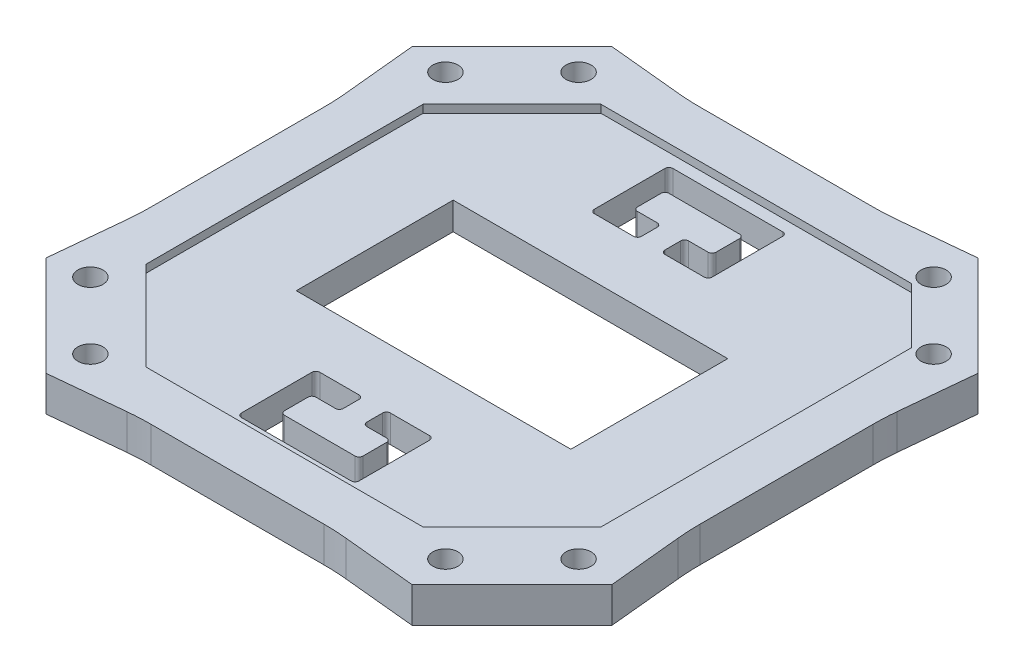
SolidWorks part; units mm, degrees
ref_plane "Front Plane" through (0, 0, 0) normal (0, 0, 1) x (1, 0, 0)
ref_plane "Top Plane" through (0, 0, 0) normal (0, 1, 0) x (1, 0, 0)
ref_plane "Right Plane" through (0, 0, 0) normal (1, 0, 0) x (0, 0, -1)
sketch "Sketch2" plane through (0, 0, 0) normal (0, 1, 0) x (1, 0, 0)
  line L0 (0, 0) -> (84.8528, 84.8528) construction
  line L1 (35, -35) -> (-35, -35) construction
  line L2 (35, -35) -> (35, 35) construction
  line L3 (35, 35) -> (-35, 35) construction
  line L4 (-35, -35) -> (-35, 35) construction
  line L5 (35, -35) -> (-35, 35) construction
  line L6 (35, 35) -> (-35, -35) construction
  line L7 (0, 35) -> (0, -35) construction
  line L8 (-12.5, 35) -> (12.5, 35)
  line L9 (35, 12.5) -> (35, -12.5)
  line L10 (12.5, -35) -> (-12.5, -35)
  line L11 (-35, -12.5) -> (-35, 12.5)
  line L12 (20.5061, 33.234) -> (33.234, 20.5061) construction
  line L13 (23.3345, 36.0624) -> (36.0624, 23.3345)
  line L14 (12.5, 35) -> (23.3345, 36.0624)
  line L15 (36.0624, 23.3345) -> (35, 12.5)
  line L16 (35, -12.5) -> (36.0624, -23.3345)
  line L17 (36.0624, -23.3345) -> (23.3345, -36.0624)
  line L18 (23.3345, -36.0624) -> (12.5, -35)
  line L19 (-12.5, -35) -> (-23.3345, -36.0624)
  line L20 (-23.3345, -36.0624) -> (-36.0624, -23.3345)
  line L21 (-36.0624, -23.3345) -> (-35, -12.5)
  line L22 (-35, 12.5) -> (-36.0624, 23.3345)
  line L23 (-36.0624, 23.3345) -> (-23.3345, 36.0624)
  line L24 (-23.3345, 36.0624) -> (-12.5, 35)
  circle A0 centre (22.6274, 31.1127) radius 1.6
  circle A1 centre (31.1127, 22.6274) radius 1.6
  circle A2 centre (22.6274, -31.1127) radius 1.6
  circle A3 centre (31.1127, -22.6274) radius 1.6
  circle A4 centre (-31.1127, -22.6274) radius 1.6
  circle A5 centre (-22.6274, -31.1127) radius 1.6
  circle A6 centre (-22.6274, 31.1127) radius 1.6
  circle A7 centre (-31.1127, 22.6274) radius 1.6
  point P0 (0, 0)
  point P21 (0, 0)
  point P54 (0, 0)
  dimension "D13" = 3.2
  dimension "D1" = 70
  dimension "D2" = 70
  dimension "D3" = 120
  dimension "D4" = 12.5
  dimension "D5" = 25
  dimension "D7" = 9
  dimension "D8" = 18
  dimension "D9" = 82
  dimension "D10" = 4
  dimension "D11" = 9
  dimension "D12" = 18
  dimension "D14" = 6
  dimension "D15" = 6
  dimension "D6" = 4
  dimension "D16" = 4
extrude "Boss-Extrude1" add sketch "Sketch2" along normal blind 4.5
sketch "Sketch3" plane through (0, 4.5, 0) normal (0, 1, 0) x (1, 0, 0)
  line L0 (0, 0) -> (0, 35) construction
  line L1 (12.5, 35) -> (-12.5, 35) construction
  line L2 (0, 0) -> (-35, 0) construction
  line L3 (-35, 12.5) -> (-35, -12.5) construction
  line L4 (-17.669, 29) -> (21.9117, 29)
  line L5 (21.9117, 29) -> (29, 21.9117)
  line L6 (29, 21.9117) -> (29, -17.669)
  line L7 (29, -17.669) -> (17.669, -29)
  line L8 (17.669, -29) -> (-17.669, -29)
  line L9 (-17.669, -29) -> (-29, -17.669)
  line L10 (-29, -17.669) -> (-29, 17.669)
  line L11 (-29, 17.669) -> (-17.669, 29)
  line L12 (-36.0624, -23.3345) -> (-23.3345, -36.0624) construction
  line L13 (-23.3345, 36.0624) -> (-36.0624, 23.3345) construction
  line L14 (36.0624, 23.3345) -> (23.3345, 36.0624) construction
  line L15 (23.3345, -36.0624) -> (36.0624, -23.3345) construction
  line L16 (35, -12.5) -> (35, 12.5) construction
  line L17 (-12.5, -35) -> (12.5, -35) construction
  dimension "D1" = 9
  dimension "D2" = 9
  dimension "D3" = 6
  dimension "D4" = 6
  dimension "D5" = 6
  dimension "D6" = 6
  dimension "D7" = 9
  dimension "D8" = 6
extrude "Cut-Extrude1" cut sketch "Sketch3" against normal blind 1
sketch "Sketch4" plane through (0, 3.5, 0) normal (0, 1, 0) x (1, 0, 0)
  line L0 (0, 0) -> (0, 29) construction
  line L1 (21.9117, 29) -> (-17.669, 29) construction
  line L2 (0, 0) -> (-29, 0) construction
  line L3 (-29, 17.669) -> (-29, -17.669) construction
  line L4 (-29, 11.2631) -> (-29, -11.2631)
  line L5 (-24.0792, -13.5676) -> (-16.0792, -6.8995)
  line L6 (-15, -4.5951) -> (-15, 4.5951)
  line L7 (-16.0792, 6.8995) -> (-24.0792, 13.5676)
  line L8 (11.2631, 29) -> (-11.2631, 29)
  line L9 (6.8995, 16.0792) -> (13.5676, 24.0792)
  line L10 (-13.5676, 24.0792) -> (-6.8995, 16.0792)
  line L11 (-4.5951, 15) -> (4.5951, 15)
  line L12 (29, -11.2631) -> (29, 11.2631)
  line L13 (16.0792, -6.8995) -> (24.0792, -13.5676)
  line L14 (24.0792, 13.5676) -> (16.0792, 6.8995)
  line L15 (15, 4.5951) -> (15, -4.5951)
  line L16 (-11.2631, -29) -> (11.2631, -29)
  line L17 (-6.8995, -16.0792) -> (-13.5676, -24.0792)
  line L18 (13.5676, -24.0792) -> (6.8995, -16.0792)
  line L19 (4.5951, -15) -> (-4.5951, -15)
  arc A0 (-15, 4.5951) -> (-16.0792, 6.8995) centre (-18, 4.5951) ccw
  arc A1 (-16.0792, -6.8995) -> (-15, -4.5951) centre (-18, -4.5951) ccw
  arc A2 (-29, -11.2631) -> (-24.0792, -13.5676) centre (-26, -11.2631) ccw
  arc A3 (-29, 11.2631) -> (-24.0792, 13.5676) centre (-26, 11.2631) cw
  arc A4 (11.2631, 29) -> (13.5676, 24.0792) centre (11.2631, 26) cw
  arc A5 (-11.2631, 29) -> (-13.5676, 24.0792) centre (-11.2631, 26) ccw
  arc A6 (4.5951, 15) -> (6.8995, 16.0792) centre (4.5951, 18) ccw
  arc A7 (-6.8995, 16.0792) -> (-4.5951, 15) centre (-4.5951, 18) ccw
  arc A8 (29, -11.2631) -> (24.0792, -13.5676) centre (26, -11.2631) cw
  arc A9 (29, 11.2631) -> (24.0792, 13.5676) centre (26, 11.2631) ccw
  arc A10 (15, -4.5951) -> (16.0792, -6.8995) centre (18, -4.5951) ccw
  arc A11 (16.0792, 6.8995) -> (15, 4.5951) centre (18, 4.5951) ccw
  arc A12 (-11.2631, -29) -> (-13.5676, -24.0792) centre (-11.2631, -26) cw
  arc A13 (11.2631, -29) -> (13.5676, -24.0792) centre (11.2631, -26) ccw
  arc A14 (-4.5951, -15) -> (-6.8995, -16.0792) centre (-4.5951, -18) ccw
  arc A15 (6.8995, -16.0792) -> (4.5951, -15) centre (4.5951, -18) ccw
  point P17 (-15, 6)
  point P20 (-15, -6)
  point P23 (-29, -17.669)
  point P26 (-29, 17.669)
  dimension "D3" = 3
  dimension "D1" = 15
  dimension "D2" = 12
  dimension "D4" = 4
extrude "Cut-Extrude2" [suppressed] cut sketch "Sketch4" against normal blind 1.2
sketch "Sketch5" plane through (0, 3.5, 0) normal (0, 1, 0) x (1, 0, 0)
  line L1 (0, 0) -> (13.2278, 0) construction
  line L2 (0, 0) -> (0, 15.25) construction
  line L3 (0, 15.25) -> (13.2278, 15.25) construction
  line L4 (13.2278, 0) -> (13.2278, 15.25) construction
  circle A0 centre (13.2278, 15.25) radius 1.5
  dimension "D2" = 3
  dimension "D1" = 15.25
extrude "Cut-Extrude3" [suppressed] cut sketch "Sketch5" against normal through all
sketch "Sketch6" [suppressed] plane through (0, 3.5, 0) normal (0, 1, 0) x (1, 0, 0)
  circle A0 centre (13.2278, 15.25) radius 4
  dimension "D1" = 8
extrude "Boss-Extrude2" [suppressed] add sketch "Sketch6" along normal blind 1.2 contours A0
ref_axis "Axis1" [suppressed] through (0, 4.935, 0) along (0, -1, 0)
pattern_circular "CirPattern1" [suppressed] count 4 over 360 about axis through (0, 4.935, 0) along (0, -1, 0) of bodies 105
fillet "Fillet1" [suppressed] radius 1
fillet "Fillet2" radius 30 8 edges at (-35, 2.25, 12.5) (-35, 2.25, -12.5) (-12.5, 2.25, -35) (12.5, 2.25, -35) (35, 2.25, -12.5) (35, 2.25, 12.5) (-12.5, 2.25, 35) (12.5, 2.25, 35)
sketch "Sketch10" plane through (0, 3.5, 0) normal (0, 1, 0) x (1, 0, 0)
  line L0 (0, -25.5325) -> (0, 25.5325) construction
  line L1 (0, 0) -> (-23.0892, 0) construction
  line L2 (-1.5, 20) -> (-1.5, 18)
  line L3 (7, 27.5) -> (-7, 27.5)
  line L4 (7.5, 27) -> (7.5, 18)
  line L5 (7, 17.5) -> (2, 17.5)
  line L6 (-7.5, 27) -> (-7.5, 18)
  line L7 (7.5, 27.5) -> (-7.5, 17.5) construction
  line L8 (7.5, 17.5) -> (-7.5, 27.5) construction
  line L9 (4.5, 20.5) -> (2, 20.5)
  line L10 (5, 21) -> (5, 24)
  line L11 (4.5, 24.5) -> (-4.5, 24.5)
  line L12 (-5, 21) -> (-5, 24)
  line L13 (5, 20.5) -> (-5, 24.5) construction
  line L14 (5, 24.5) -> (-5, 20.5) construction
  line L15 (1.5, 20) -> (1.5, 18)
  line L16 (-2, 17.5) -> (-7, 17.5)
  line L17 (-2, 20.5) -> (-4.5, 20.5)
  line L18 (5, -24.5) -> (-5, -20.5) construction
  line L19 (5, -20.5) -> (-5, -24.5) construction
  line L20 (7.5, -17.5) -> (-7.5, -27.5) construction
  line L21 (7.5, -27.5) -> (-7.5, -17.5) construction
  line L22 (-2, -20.5) -> (-4.5, -20.5)
  line L23 (-2, -17.5) -> (-7, -17.5)
  line L24 (1.5, -20) -> (1.5, -18)
  line L25 (-5, -21) -> (-5, -24)
  line L26 (4.5, -24.5) -> (-4.5, -24.5)
  line L27 (5, -21) -> (5, -24)
  line L28 (4.5, -20.5) -> (2, -20.5)
  line L29 (-7.5, -27) -> (-7.5, -18)
  line L30 (7, -17.5) -> (2, -17.5)
  line L31 (7, -27.5) -> (-7, -27.5)
  line L32 (-1.5, -20) -> (-1.5, -18)
  line L33 (7.5, -27) -> (7.5, -18)
  arc A0 (1.5, 18) -> (2, 17.5) centre (2, 18) ccw
  arc A1 (1.5, 20) -> (2, 20.5) centre (2, 20) cw
  arc A2 (-1.5, 18) -> (-2, 17.5) centre (-2, 18) cw
  arc A3 (-1.5, 20) -> (-2, 20.5) centre (-2, 20) ccw
  arc A4 (-4.5, 20.5) -> (-5, 21) centre (-4.5, 21) cw
  arc A5 (5, 24) -> (4.5, 24.5) centre (4.5, 24) ccw
  arc A6 (4.5, 20.5) -> (5, 21) centre (4.5, 21) ccw
  arc A7 (-4.5, 24.5) -> (-5, 24) centre (-4.5, 24) ccw
  arc A8 (-7, 27.5) -> (-7.5, 27) centre (-7, 27) ccw
  arc A9 (7.5, 18) -> (7, 17.5) centre (7, 18) cw
  arc A10 (7, 27.5) -> (7.5, 27) centre (7, 27) cw
  arc A11 (-7, 17.5) -> (-7.5, 18) centre (-7, 18) cw
  arc A12 (-7, -17.5) -> (-7.5, -18) centre (-7, -18) ccw
  arc A13 (7, -27.5) -> (7.5, -27) centre (7, -27) ccw
  arc A14 (7.5, -18) -> (7, -17.5) centre (7, -18) ccw
  arc A15 (-7, -27.5) -> (-7.5, -27) centre (-7, -27) cw
  arc A16 (-4.5, -24.5) -> (-5, -24) centre (-4.5, -24) cw
  arc A17 (4.5, -20.5) -> (5, -21) centre (4.5, -21) cw
  arc A18 (5, -24) -> (4.5, -24.5) centre (4.5, -24) cw
  arc A19 (-4.5, -20.5) -> (-5, -21) centre (-4.5, -21) ccw
  arc A20 (-1.5, -20) -> (-2, -20.5) centre (-2, -20) cw
  arc A21 (-1.5, -18) -> (-2, -17.5) centre (-2, -18) ccw
  arc A22 (1.5, -20) -> (2, -20.5) centre (2, -20) ccw
  arc A23 (1.5, -18) -> (2, -17.5) centre (2, -18) cw
  point P3 (0, 22.5)
  point P9 (0, 22.5)
  point P20 (1.5, 17.5)
  point P23 (1.5, 20.5)
  point P26 (-1.5, 17.5)
  point P29 (-1.5, 20.5)
  point P99 (-1.5, -20.5)
  point P100 (-1.5, -17.5)
  point P101 (1.5, -20.5)
  point P102 (1.5, -17.5)
  point P103 (0, -22.5)
  dimension "D7" = 0.5
  dimension "D1" = 17.5
  dimension "D2" = 10
  dimension "D3" = 15
  dimension "D4" = 2.5
  dimension "D5" = 3
  dimension "D6" = 6
extrude "Cut-Extrude4" cut sketch "Sketch10" against normal through all
sketch "Sketch11" plane through (0, 3.5, 0) normal (0, 1, 0) x (1, 0, 0)
  line L1 (17.5, -10) -> (-17.5, -10)
  line L2 (17.5, -10) -> (17.5, 10)
  line L3 (17.5, 10) -> (-17.5, 10)
  line L4 (-17.5, -10) -> (-17.5, 10)
  line L5 (17.5, -10) -> (-17.5, 10) construction
  line L6 (17.5, 10) -> (-17.5, -10) construction
  point P0 (0, 0)
  dimension "D1" = 20
  dimension "D2" = 35
extrude "Cut-Extrude5" cut sketch "Sketch11" against normal through all
